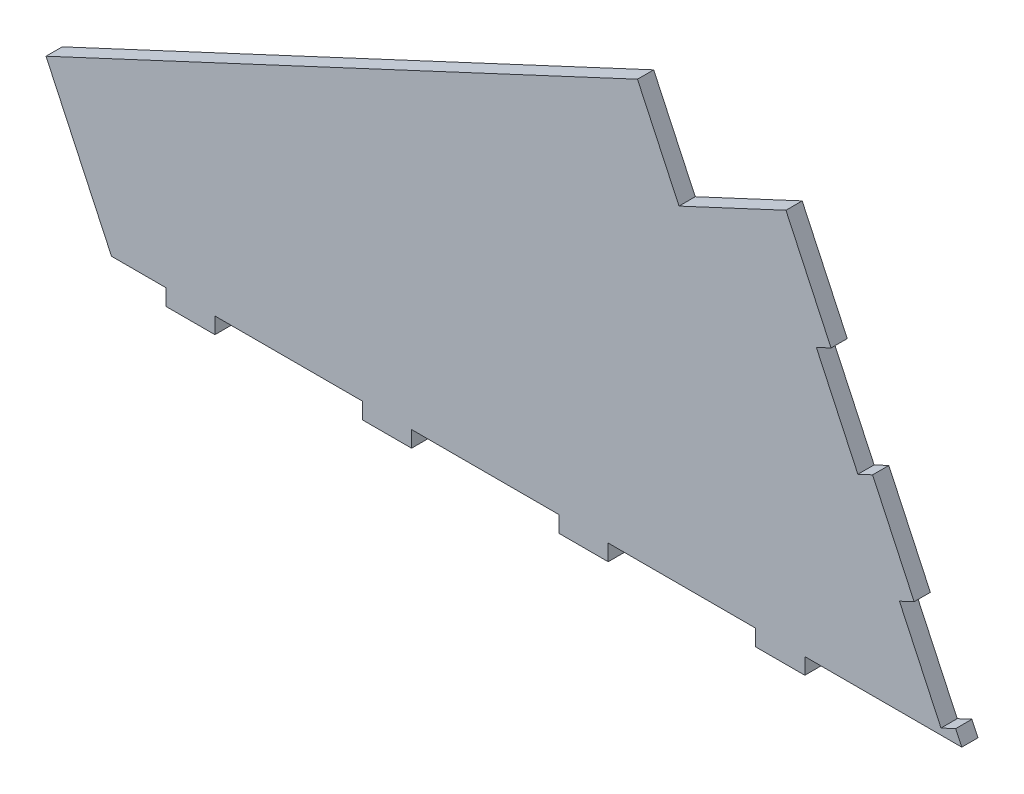
SolidWorks part; units mm, degrees
material "Balsa"
ref_plane "Front Plane" through (0, 0, 0) normal (0, 0, 1) x (1, 0, 0)
ref_plane "Top Plane" through (0, 0, 0) normal (0, 1, 0) x (1, 0, 0)
ref_plane "Right Plane" through (0, 0, 0) normal (1, 0, 0) x (0, 0, -1)
sketch "Sketch1" plane through (0, 0, 0) normal (0, 0, 1) x (1, 0, 0)
  line L0 (321.5462, 12.6346) -> (148.586, 12.6346)
  line L1 (148.586, 12.6346) -> (135.2566, 41.2196)
  line L2 (135.2566, 41.2196) -> (255.5737, 97.3243)
  line L3 (-63.4467, -51.4373) -> (255.5737, 97.3243) construction
  line L4 (255.5737, 97.3243) -> (264.026, 79.1982)
  line L5 (264.026, 79.1982) -> (285.7774, 89.341)
  line L6 (285.7774, 89.341) -> (321.5462, 12.6346)
  line L7 (327.4362, 0.0035) -> (398.701, -152.8244) construction
  line L9 (285.7774, 89.341) -> (294.9517, 69.6668) construction
  line L11 (135.2566, 41.2196) -> (148.586, 12.6346) construction
  line L12 (174.6178, 12.6346) -> (194.6178, 12.6346) construction
  dimension "D1" = 24
  dimension "D2" = 20
extrude "Boss-Extrude1" add sketch "Sketch1" against normal blind 3.3
sketch "Sketch2" plane through (0, 0, 0) normal (0, 0, 1) x (1, 0, 0)
  line L0 (303.404, 51.5407) -> (294.9517, 69.6668)
  line L1 (303.404, 51.5407) -> (300.4132, 50.146)
  line L2 (294.9517, 69.6668) -> (291.9609, 68.2722)
  line L3 (300.4132, 50.146) -> (291.9609, 68.2722)
  line L4 (320.3088, 15.2883) -> (311.8564, 33.4145)
  line L5 (320.3088, 15.2883) -> (317.3179, 13.8937)
  line L6 (311.8564, 33.4145) -> (308.8656, 32.0199)
  line L7 (317.3179, 13.8937) -> (308.8656, 32.0199)
  dimension "D1" = 3.3
  dimension "D2" = 3.3
extrude "Cut-Extrude1" cut sketch "Sketch2" against normal blind 3.3
sketch "Sketch3" plane through (0, 0, 0) normal (0, 0, 1) x (1, 0, 0)
  line L0 (289.6178, 9.3346) -> (279.6178, 9.3346)
  line L1 (289.6178, 9.3346) -> (289.6178, 13.052)
  line L2 (279.6178, 9.3346) -> (279.6178, 13.052)
  line L3 (289.6178, 13.052) -> (279.6178, 13.052)
  line L4 (249.6178, 9.3346) -> (239.6178, 9.3346)
  line L5 (249.6178, 9.3346) -> (249.6178, 12.9084)
  line L6 (239.6178, 9.3346) -> (239.6178, 12.9084)
  line L7 (249.6178, 12.9084) -> (239.6178, 12.9084)
  line L8 (209.6178, 9.3346) -> (199.6178, 9.3346)
  line L9 (209.6178, 9.3346) -> (209.6178, 13.0454)
  line L10 (199.6178, 9.3346) -> (199.6178, 13.0454)
  line L11 (209.6178, 13.0454) -> (199.6178, 13.0454)
  line L12 (169.6178, 9.3346) -> (159.6178, 9.3346)
  line L13 (169.6178, 9.3346) -> (169.6178, 12.8442)
  line L14 (159.6178, 9.3346) -> (159.6178, 12.8442)
  line L15 (169.6178, 12.8442) -> (159.6178, 12.8442)
extrude "Boss-Extrude2" add sketch "Sketch3" against normal blind 3.3
